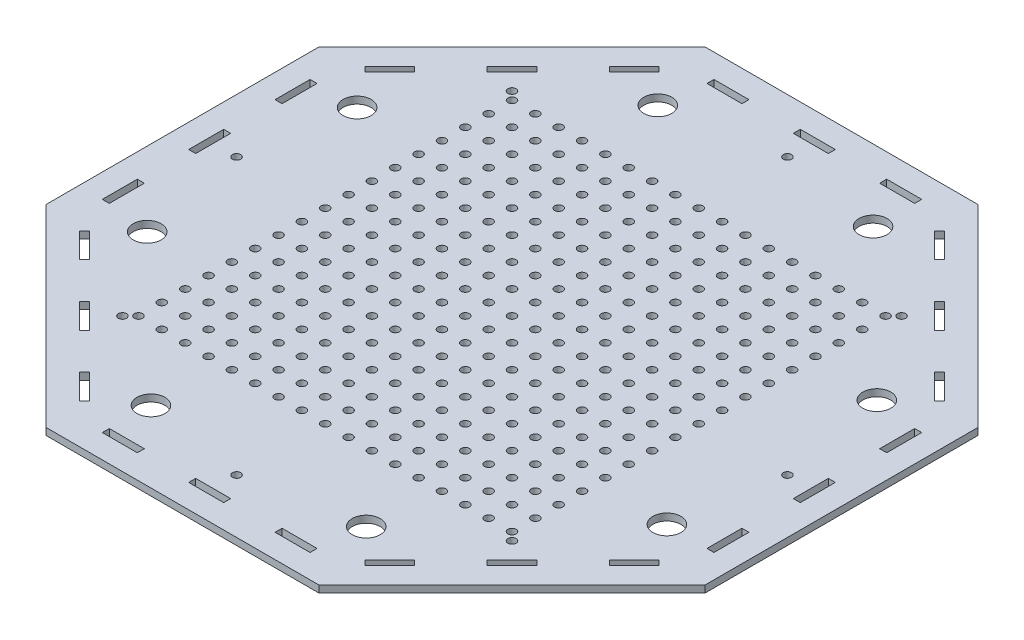
SolidWorks part; units mm, degrees
material "Акрил (Средняя-высокая ударопрочность)"
ref_plane "Спереди" through (0, 0, 0) normal (0, 0, 1) x (1, 0, 0)
ref_plane "Сверху" through (0, 0, 0) normal (0, 1, 0) x (1, 0, 0)
ref_plane "Справа" through (0, 0, 0) normal (1, 0, 0) x (0, 0, -1)
sketch "Эскиз1" plane through (0, 0, 0) normal (0, 1, 0) x (1, 0, 0)
  line L30 (141.149, -58.4658) -> (141.149, 58.4658)
  line L31 (141.149, 58.4658) -> (58.4658, 141.149)
  line L36 (58.4658, 141.149) -> (-58.4658, 141.149)
  line L37 (-58.4658, 141.149) -> (-141.149, 58.4658)
  line L38 (-141.149, 58.4658) -> (-141.149, -58.4658)
  line L39 (-141.149, -58.4658) -> (-58.4658, -141.149)
  line L40 (-58.4658, -141.149) -> (58.4658, -141.149)
  line L41 (58.4658, -141.149) -> (141.149, -58.4658)
  line L42 (-7.5, 128) -> (7.5, 128)
  line L44 (7.5, 128) -> (7.5, 131)
  line L45 (-7.5, 131) -> (7.5, 131)
  line L46 (7.5, 129.5) -> (18.5, 129.5)
  line L47 (18.5, 129.5) -> (18.5, 99.2986)
  line L48 (-7.5, 128) -> (-7.5, 131)
  line L49 (44.5, 128) -> (44.5, 131)
  line L50 (44.5, 131) -> (29.5, 131)
  line L51 (29.5, 128) -> (29.5, 131)
  line L52 (-44.5, 128) -> (-29.5, 128)
  line L53 (44.5, 128) -> (29.5, 128)
  line L54 (-29.5, 128) -> (-29.5, 131)
  line L55 (-44.5, 131) -> (-29.5, 131)
  line L56 (-44.5, 128) -> (-44.5, 131)
  line L57 (85.2064, 95.813) -> (95.813, 85.2064)
  line L58 (95.813, 85.2064) -> (97.9343, 87.3277)
  line L59 (87.3277, 97.9343) -> (97.9343, 87.3277)
  line L60 (96.8736, 86.267) -> (104.6518, 78.4889)
  line L61 (85.2064, 95.813) -> (87.3277, 97.9343)
  line L62 (121.9759, 59.0434) -> (124.0972, 61.1647)
  line L63 (124.0972, 61.1647) -> (113.4906, 71.7713)
  line L64 (111.3693, 69.65) -> (113.4906, 71.7713)
  line L65 (59.0434, 121.9759) -> (69.65, 111.3693)
  line L66 (121.9759, 59.0434) -> (111.3693, 69.65)
  line L67 (69.65, 111.3693) -> (71.7713, 113.4906)
  line L68 (61.1647, 124.0972) -> (71.7713, 113.4906)
  line L69 (59.0434, 121.9759) -> (61.1647, 124.0972)
  line L70 (128, 7.5) -> (128, -7.5)
  line L71 (128, -7.5) -> (131, -7.5)
  line L72 (131, 7.5) -> (131, -7.5)
  line L73 (129.5, -7.5) -> (129.5, -18.5)
  line L74 (128, 7.5) -> (131, 7.5)
  line L75 (128, -44.5) -> (131, -44.5)
  line L76 (131, -44.5) -> (131, -29.5)
  line L77 (128, -29.5) -> (131, -29.5)
  line L78 (128, 44.5) -> (128, 29.5)
  line L79 (128, -44.5) -> (128, -29.5)
  line L80 (128, 29.5) -> (131, 29.5)
  line L81 (131, 44.5) -> (131, 29.5)
  line L82 (128, 44.5) -> (131, 44.5)
  line L83 (95.813, -85.2064) -> (85.2064, -95.813)
  line L84 (85.2064, -95.813) -> (87.3277, -97.9343)
  line L85 (97.9343, -87.3277) -> (87.3277, -97.9343)
  line L86 (86.267, -96.8736) -> (78.4889, -104.6518)
  line L87 (95.813, -85.2064) -> (97.9343, -87.3277)
  line L88 (59.0434, -121.9759) -> (61.1647, -124.0972)
  line L89 (61.1647, -124.0972) -> (71.7713, -113.4906)
  line L90 (69.65, -111.3693) -> (71.7713, -113.4906)
  line L91 (121.9759, -59.0434) -> (111.3693, -69.65)
  line L92 (59.0434, -121.9759) -> (69.65, -111.3693)
  line L93 (111.3693, -69.65) -> (113.4906, -71.7713)
  line L94 (124.0972, -61.1647) -> (113.4906, -71.7713)
  line L95 (121.9759, -59.0434) -> (124.0972, -61.1647)
  line L96 (7.5, -128) -> (-7.5, -128)
  line L97 (-7.5, -128) -> (-7.5, -131)
  line L98 (7.5, -131) -> (-7.5, -131)
  line L99 (-7.5, -129.5) -> (-18.5, -129.5)
  line L100 (7.5, -128) -> (7.5, -131)
  line L101 (-44.5, -128) -> (-44.5, -131)
  line L102 (-44.5, -131) -> (-29.5, -131)
  line L103 (-29.5, -128) -> (-29.5, -131)
  line L104 (44.5, -128) -> (29.5, -128)
  line L105 (-44.5, -128) -> (-29.5, -128)
  line L106 (29.5, -128) -> (29.5, -131)
  line L107 (44.5, -131) -> (29.5, -131)
  line L108 (44.5, -128) -> (44.5, -131)
  line L109 (-85.2064, -95.813) -> (-95.813, -85.2064)
  line L110 (-95.813, -85.2064) -> (-97.9343, -87.3277)
  line L111 (-87.3277, -97.9343) -> (-97.9343, -87.3277)
  line L112 (-96.8736, -86.267) -> (-104.6518, -78.4889)
  line L113 (-85.2064, -95.813) -> (-87.3277, -97.9343)
  line L114 (-121.9759, -59.0434) -> (-124.0972, -61.1647)
  line L115 (-124.0972, -61.1647) -> (-113.4906, -71.7713)
  line L116 (-111.3693, -69.65) -> (-113.4906, -71.7713)
  line L117 (-59.0434, -121.9759) -> (-69.65, -111.3693)
  line L118 (-121.9759, -59.0434) -> (-111.3693, -69.65)
  line L119 (-69.65, -111.3693) -> (-71.7713, -113.4906)
  line L120 (-61.1647, -124.0972) -> (-71.7713, -113.4906)
  line L121 (-59.0434, -121.9759) -> (-61.1647, -124.0972)
  line L122 (-128, -7.5) -> (-128, 7.5)
  line L123 (-128, 7.5) -> (-131, 7.5)
  line L124 (-131, -7.5) -> (-131, 7.5)
  line L125 (-129.5, 7.5) -> (-129.5, 18.5)
  line L126 (-128, -7.5) -> (-131, -7.5)
  line L127 (-128, 44.5) -> (-131, 44.5)
  line L128 (-131, 44.5) -> (-131, 29.5)
  line L129 (-128, 29.5) -> (-131, 29.5)
  line L130 (-128, -44.5) -> (-128, -29.5)
  line L131 (-128, 44.5) -> (-128, 29.5)
  line L132 (-128, -29.5) -> (-131, -29.5)
  line L133 (-131, -44.5) -> (-131, -29.5)
  line L134 (-128, -44.5) -> (-131, -44.5)
  line L135 (-95.813, 85.2064) -> (-85.2064, 95.813)
  line L136 (-85.2064, 95.813) -> (-87.3277, 97.9343)
  line L137 (-97.9343, 87.3277) -> (-87.3277, 97.9343)
  line L138 (-86.267, 96.8736) -> (-78.4889, 104.6518)
  line L139 (-95.813, 85.2064) -> (-97.9343, 87.3277)
  line L140 (-59.0434, 121.9759) -> (-61.1647, 124.0972)
  line L141 (-61.1647, 124.0972) -> (-71.7713, 113.4906)
  line L142 (-69.65, 111.3693) -> (-71.7713, 113.4906)
  line L143 (-121.9759, 59.0434) -> (-111.3693, 69.65)
  line L144 (-59.0434, 121.9759) -> (-69.65, 111.3693)
  line L145 (-111.3693, 69.65) -> (-113.4906, 71.7713)
  line L146 (-124.0972, 61.1647) -> (-113.4906, 71.7713)
  line L147 (-121.9759, 59.0434) -> (-124.0972, 61.1647)
  circle A0 centre (0, 0) radius 152.7786 construction
  circle A1 centre (44.1547, 110.505) radius 6
  circle A2 centre (0, 118) radius 1.75
  circle A3 centre (83.4386, 83.4386) radius 1.75
  circle A4 centre (109.3609, 46.9168) radius 6
  circle A5 centre (118, 0) radius 1.75
  circle A6 centre (110.505, -44.1547) radius 6
  circle A7 centre (83.4386, -83.4386) radius 1.75
  circle A8 centre (46.9168, -109.3609) radius 6
  circle A9 centre (0, -118) radius 1.75
  circle A10 centre (-44.1547, -110.505) radius 6
  circle A11 centre (-83.4386, -83.4386) radius 1.75
  circle A12 centre (-109.3609, -46.9168) radius 6
  circle A13 centre (-118, 0) radius 1.75
  circle A14 centre (-110.505, 44.1547) radius 6
  circle A15 centre (-83.4386, 83.4386) radius 1.75
  circle A16 centre (-46.9168, 109.3609) radius 6
  circle A17 centre (0, 0) radius 1.75
  circle A18 centre (10, 0) radius 1.75
  circle A19 centre (20, 0) radius 1.75
  circle A20 centre (30, 0) radius 1.75
  circle A21 centre (40, 0) radius 1.75
  circle A22 centre (50, 0) radius 1.75
  circle A23 centre (60, 0) radius 1.75
  circle A24 centre (70, 0) radius 1.75
  circle A25 centre (80, 0) radius 1.75
  circle A26 centre (10, 10) radius 1.75
  circle A27 centre (20, 10) radius 1.75
  circle A28 centre (30, 10) radius 1.75
  circle A29 centre (40, 10) radius 1.75
  circle A30 centre (50, 10) radius 1.75
  circle A31 centre (60, 10) radius 1.75
  circle A32 centre (70, 10) radius 1.75
  circle A33 centre (80, 10) radius 1.75
  circle A34 centre (10, 20) radius 1.75
  circle A35 centre (20, 20) radius 1.75
  circle A36 centre (30, 20) radius 1.75
  circle A37 centre (40, 20) radius 1.75
  circle A38 centre (50, 20) radius 1.75
  circle A39 centre (60, 20) radius 1.75
  circle A40 centre (70, 20) radius 1.75
  circle A41 centre (80, 20) radius 1.75
  circle A42 centre (10, 30) radius 1.75
  circle A43 centre (20, 30) radius 1.75
  circle A44 centre (30, 30) radius 1.75
  circle A45 centre (40, 30) radius 1.75
  circle A46 centre (50, 30) radius 1.75
  circle A47 centre (60, 30) radius 1.75
  circle A48 centre (70, 30) radius 1.75
  circle A49 centre (80, 30) radius 1.75
  circle A50 centre (10, 40) radius 1.75
  circle A51 centre (20, 40) radius 1.75
  circle A52 centre (30, 40) radius 1.75
  circle A53 centre (40, 40) radius 1.75
  circle A54 centre (50, 40) radius 1.75
  circle A55 centre (60, 40) radius 1.75
  circle A56 centre (70, 40) radius 1.75
  circle A57 centre (80, 40) radius 1.75
  circle A58 centre (10, 50) radius 1.75
  circle A59 centre (20, 50) radius 1.75
  circle A60 centre (30, 50) radius 1.75
  circle A61 centre (40, 50) radius 1.75
  circle A62 centre (50, 50) radius 1.75
  circle A63 centre (60, 50) radius 1.75
  circle A64 centre (70, 50) radius 1.75
  circle A65 centre (80, 50) radius 1.75
  circle A66 centre (10, 60) radius 1.75
  circle A67 centre (20, 60) radius 1.75
  circle A68 centre (30, 60) radius 1.75
  circle A69 centre (40, 60) radius 1.75
  circle A70 centre (50, 60) radius 1.75
  circle A71 centre (60, 60) radius 1.75
  circle A72 centre (70, 60) radius 1.75
  circle A73 centre (80, 60) radius 1.75
  circle A74 centre (10, 70) radius 1.75
  circle A75 centre (20, 70) radius 1.75
  circle A76 centre (30, 70) radius 1.75
  circle A77 centre (40, 70) radius 1.75
  circle A78 centre (50, 70) radius 1.75
  circle A79 centre (60, 70) radius 1.75
  circle A80 centre (70, 70) radius 1.75
  circle A81 centre (80, 70) radius 1.75
  circle A82 centre (10, 80) radius 1.75
  circle A83 centre (20, 80) radius 1.75
  circle A84 centre (30, 80) radius 1.75
  circle A85 centre (40, 80) radius 1.75
  circle A86 centre (50, 80) radius 1.75
  circle A87 centre (60, 80) radius 1.75
  circle A88 centre (70, 80) radius 1.75
  circle A89 centre (80, 80) radius 1.75
  circle A90 centre (0, 10) radius 1.75
  circle A91 centre (0, 20) radius 1.75
  circle A92 centre (0, 30) radius 1.75
  circle A93 centre (0, 40) radius 1.75
  circle A94 centre (0, 50) radius 1.75
  circle A95 centre (0, 60) radius 1.75
  circle A96 centre (0, 70) radius 1.75
  circle A97 centre (0, 80) radius 1.75
  circle A98 centre (-10, 0) radius 1.75
  circle A99 centre (-20, 0) radius 1.75
  circle A100 centre (-30, 0) radius 1.75
  circle A101 centre (-40, 0) radius 1.75
  circle A102 centre (-50, 0) radius 1.75
  circle A103 centre (-60, 0) radius 1.75
  circle A104 centre (-70, 0) radius 1.75
  circle A105 centre (-80, 0) radius 1.75
  circle A106 centre (-10, 10) radius 1.75
  circle A107 centre (-20, 10) radius 1.75
  circle A108 centre (-30, 10) radius 1.75
  circle A109 centre (-40, 10) radius 1.75
  circle A110 centre (-50, 10) radius 1.75
  circle A111 centre (-60, 10) radius 1.75
  circle A112 centre (-70, 10) radius 1.75
  circle A113 centre (-80, 10) radius 1.75
  circle A114 centre (-10, 20) radius 1.75
  circle A115 centre (-20, 20) radius 1.75
  circle A116 centre (-30, 20) radius 1.75
  circle A117 centre (-40, 20) radius 1.75
  circle A118 centre (-50, 20) radius 1.75
  circle A119 centre (-60, 20) radius 1.75
  circle A120 centre (-70, 20) radius 1.75
  circle A121 centre (-80, 20) radius 1.75
  circle A122 centre (-10, 30) radius 1.75
  circle A123 centre (-20, 30) radius 1.75
  circle A124 centre (-30, 30) radius 1.75
  circle A125 centre (-40, 30) radius 1.75
  circle A126 centre (-50, 30) radius 1.75
  circle A127 centre (-60, 30) radius 1.75
  circle A128 centre (-70, 30) radius 1.75
  circle A129 centre (-80, 30) radius 1.75
  circle A130 centre (-10, 40) radius 1.75
  circle A131 centre (-20, 40) radius 1.75
  circle A132 centre (-30, 40) radius 1.75
  circle A133 centre (-40, 40) radius 1.75
  circle A134 centre (-50, 40) radius 1.75
  circle A135 centre (-60, 40) radius 1.75
  circle A136 centre (-70, 40) radius 1.75
  circle A137 centre (-80, 40) radius 1.75
  circle A138 centre (-10, 50) radius 1.75
  circle A139 centre (-20, 50) radius 1.75
  circle A140 centre (-30, 50) radius 1.75
  circle A141 centre (-40, 50) radius 1.75
  circle A142 centre (-50, 50) radius 1.75
  circle A143 centre (-60, 50) radius 1.75
  circle A144 centre (-70, 50) radius 1.75
  circle A145 centre (-80, 50) radius 1.75
  circle A146 centre (-10, 60) radius 1.75
  circle A147 centre (-20, 60) radius 1.75
  circle A148 centre (-30, 60) radius 1.75
  circle A149 centre (-40, 60) radius 1.75
  circle A150 centre (-50, 60) radius 1.75
  circle A151 centre (-60, 60) radius 1.75
  circle A152 centre (-70, 60) radius 1.75
  circle A153 centre (-80, 60) radius 1.75
  circle A154 centre (-10, 70) radius 1.75
  circle A155 centre (-20, 70) radius 1.75
  circle A156 centre (-30, 70) radius 1.75
  circle A157 centre (-40, 70) radius 1.75
  circle A158 centre (-50, 70) radius 1.75
  circle A159 centre (-60, 70) radius 1.75
  circle A160 centre (-70, 70) radius 1.75
  circle A161 centre (-80, 70) radius 1.75
  circle A162 centre (-10, 80) radius 1.75
  circle A163 centre (-20, 80) radius 1.75
  circle A164 centre (-30, 80) radius 1.75
  circle A165 centre (-40, 80) radius 1.75
  circle A166 centre (-50, 80) radius 1.75
  circle A167 centre (-60, 80) radius 1.75
  circle A168 centre (-70, 80) radius 1.75
  circle A169 centre (-80, 80) radius 1.75
  circle A170 centre (0, 10) radius 1.75
  circle A171 centre (0, 20) radius 1.75
  circle A172 centre (0, 30) radius 1.75
  circle A173 centre (0, 40) radius 1.75
  circle A174 centre (0, 50) radius 1.75
  circle A175 centre (0, 60) radius 1.75
  circle A176 centre (0, 70) radius 1.75
  circle A177 centre (0, 80) radius 1.75
  circle A178 centre (-70, 0) radius 1.75
  circle A179 centre (-60, 0) radius 1.75
  circle A180 centre (-50, 0) radius 1.75
  circle A181 centre (-40, 0) radius 1.75
  circle A182 centre (-30, 0) radius 1.75
  circle A183 centre (-20, 0) radius 1.75
  circle A184 centre (-10, 0) radius 1.75
  circle A185 centre (0, 0) radius 1.75
  circle A186 centre (10, 0) radius 1.75
  circle A187 centre (20, 0) radius 1.75
  circle A188 centre (30, 0) radius 1.75
  circle A189 centre (40, 0) radius 1.75
  circle A190 centre (50, 0) radius 1.75
  circle A191 centre (60, 0) radius 1.75
  circle A192 centre (70, 0) radius 1.75
  circle A193 centre (80, 0) radius 1.75
  circle A194 centre (-70, -10) radius 1.75
  circle A195 centre (-60, -10) radius 1.75
  circle A196 centre (-50, -10) radius 1.75
  circle A197 centre (-40, -10) radius 1.75
  circle A198 centre (-30, -10) radius 1.75
  circle A199 centre (-20, -10) radius 1.75
  circle A200 centre (-10, -10) radius 1.75
  circle A201 centre (0, -10) radius 1.75
  circle A202 centre (10, -10) radius 1.75
  circle A203 centre (20, -10) radius 1.75
  circle A204 centre (30, -10) radius 1.75
  circle A205 centre (40, -10) radius 1.75
  circle A206 centre (50, -10) radius 1.75
  circle A207 centre (60, -10) radius 1.75
  circle A208 centre (70, -10) radius 1.75
  circle A209 centre (80, -10) radius 1.75
  circle A210 centre (-70, -20) radius 1.75
  circle A211 centre (-60, -20) radius 1.75
  circle A212 centre (-50, -20) radius 1.75
  circle A213 centre (-40, -20) radius 1.75
  circle A214 centre (-30, -20) radius 1.75
  circle A215 centre (-20, -20) radius 1.75
  circle A216 centre (-10, -20) radius 1.75
  circle A217 centre (0, -20) radius 1.75
  circle A218 centre (10, -20) radius 1.75
  circle A219 centre (20, -20) radius 1.75
  circle A220 centre (30, -20) radius 1.75
  circle A221 centre (40, -20) radius 1.75
  circle A222 centre (50, -20) radius 1.75
  circle A223 centre (60, -20) radius 1.75
  circle A224 centre (70, -20) radius 1.75
  circle A225 centre (80, -20) radius 1.75
  circle A226 centre (-70, -30) radius 1.75
  circle A227 centre (-60, -30) radius 1.75
  circle A228 centre (-50, -30) radius 1.75
  circle A229 centre (-40, -30) radius 1.75
  circle A230 centre (-30, -30) radius 1.75
  circle A231 centre (-20, -30) radius 1.75
  circle A232 centre (-10, -30) radius 1.75
  circle A233 centre (0, -30) radius 1.75
  circle A234 centre (10, -30) radius 1.75
  circle A235 centre (20, -30) radius 1.75
  circle A236 centre (30, -30) radius 1.75
  circle A237 centre (40, -30) radius 1.75
  circle A238 centre (50, -30) radius 1.75
  circle A239 centre (60, -30) radius 1.75
  circle A240 centre (70, -30) radius 1.75
  circle A241 centre (80, -30) radius 1.75
  circle A242 centre (-70, -40) radius 1.75
  circle A243 centre (-60, -40) radius 1.75
  circle A244 centre (-50, -40) radius 1.75
  circle A245 centre (-40, -40) radius 1.75
  circle A246 centre (-30, -40) radius 1.75
  circle A247 centre (-20, -40) radius 1.75
  circle A248 centre (-10, -40) radius 1.75
  circle A249 centre (0, -40) radius 1.75
  circle A250 centre (10, -40) radius 1.75
  circle A251 centre (20, -40) radius 1.75
  circle A252 centre (30, -40) radius 1.75
  circle A253 centre (40, -40) radius 1.75
  circle A254 centre (50, -40) radius 1.75
  circle A255 centre (60, -40) radius 1.75
  circle A256 centre (70, -40) radius 1.75
  circle A257 centre (80, -40) radius 1.75
  circle A258 centre (-70, -50) radius 1.75
  circle A259 centre (-60, -50) radius 1.75
  circle A260 centre (-50, -50) radius 1.75
  circle A261 centre (-40, -50) radius 1.75
  circle A262 centre (-30, -50) radius 1.75
  circle A263 centre (-20, -50) radius 1.75
  circle A264 centre (-10, -50) radius 1.75
  circle A265 centre (0, -50) radius 1.75
  circle A266 centre (10, -50) radius 1.75
  circle A267 centre (20, -50) radius 1.75
  circle A268 centre (30, -50) radius 1.75
  circle A269 centre (40, -50) radius 1.75
  circle A270 centre (50, -50) radius 1.75
  circle A271 centre (60, -50) radius 1.75
  circle A272 centre (70, -50) radius 1.75
  circle A273 centre (80, -50) radius 1.75
  circle A274 centre (-70, -60) radius 1.75
  circle A275 centre (-60, -60) radius 1.75
  circle A276 centre (-50, -60) radius 1.75
  circle A277 centre (-40, -60) radius 1.75
  circle A278 centre (-30, -60) radius 1.75
  circle A279 centre (-20, -60) radius 1.75
  circle A280 centre (-10, -60) radius 1.75
  circle A281 centre (0, -60) radius 1.75
  circle A282 centre (10, -60) radius 1.75
  circle A283 centre (20, -60) radius 1.75
  circle A284 centre (30, -60) radius 1.75
  circle A285 centre (40, -60) radius 1.75
  circle A286 centre (50, -60) radius 1.75
  circle A287 centre (60, -60) radius 1.75
  circle A288 centre (70, -60) radius 1.75
  circle A289 centre (80, -60) radius 1.75
  circle A290 centre (-70, -70) radius 1.75
  circle A291 centre (-60, -70) radius 1.75
  circle A292 centre (-50, -70) radius 1.75
  circle A293 centre (-40, -70) radius 1.75
  circle A294 centre (-30, -70) radius 1.75
  circle A295 centre (-20, -70) radius 1.75
  circle A296 centre (-10, -70) radius 1.75
  circle A297 centre (0, -70) radius 1.75
  circle A298 centre (10, -70) radius 1.75
  circle A299 centre (20, -70) radius 1.75
  circle A300 centre (30, -70) radius 1.75
  circle A301 centre (40, -70) radius 1.75
  circle A302 centre (50, -70) radius 1.75
  circle A303 centre (60, -70) radius 1.75
  circle A304 centre (70, -70) radius 1.75
  circle A305 centre (80, -70) radius 1.75
  circle A306 centre (-70, -80) radius 1.75
  circle A307 centre (-60, -80) radius 1.75
  circle A308 centre (-50, -80) radius 1.75
  circle A309 centre (-40, -80) radius 1.75
  circle A310 centre (-30, -80) radius 1.75
  circle A311 centre (-20, -80) radius 1.75
  circle A312 centre (-10, -80) radius 1.75
  circle A313 centre (0, -80) radius 1.75
  circle A314 centre (10, -80) radius 1.75
  circle A315 centre (20, -80) radius 1.75
  circle A316 centre (30, -80) radius 1.75
  circle A317 centre (40, -80) radius 1.75
  circle A318 centre (50, -80) radius 1.75
  circle A319 centre (60, -80) radius 1.75
  circle A320 centre (70, -80) radius 1.75
  circle A321 centre (80, -80) radius 1.75
  circle A322 centre (-80, -10) radius 1.75
  circle A323 centre (-80, -20) radius 1.75
  circle A324 centre (-80, -30) radius 1.75
  circle A325 centre (-80, -40) radius 1.75
  circle A326 centre (-80, -50) radius 1.75
  circle A327 centre (-80, -60) radius 1.75
  circle A328 centre (-80, -70) radius 1.75
  circle A329 centre (-80, -80) radius 1.75
  dimension "D2" = 8
  dimension "D3" = 9
  dimension "D1" = 8
  dimension "D4" = 9
  dimension "D5" = 9
  dimension "D6" = 9
  dimension "D7" = 17
  dimension "D8" = 9
extrude "Бобышка-Вытянуть1" add sketch "Эскиз1" along normal blind 1.5 and the other way blind 1.5 contours L40 L41 L30 L31 L36 L37 L38 L39 A329 A328 A327 A326 A325 A324 A323 A322 A321 A320 A319 A318 A317 A316 A315 A314 A313 A312 A311 A310 A309 region at (96.9844, 0, 96.9844)
